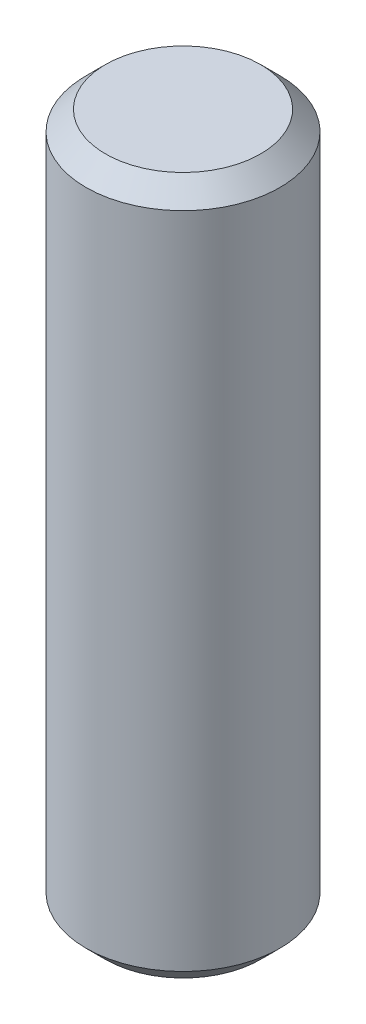
SolidWorks part; units mm, degrees
ref_plane "前视基准面" through (0, 0, 0) normal (0, 0, 1) x (1, 0, 0)
ref_plane "上视基准面" through (0, 0, 0) normal (0, 1, 0) x (1, 0, 0)
ref_plane "右视基准面" through (0, 0, 0) normal (1, 0, 0) x (0, 0, -1)
other "Configuration Table"
sketch "草图1" plane through (0, 0, 0) normal (0, 0, 1) x (1, 0, 0)
  line L0 (0, 23.0737) -> (0, -19.8109) construction
  line L1 (0, 23) -> (5, 23)
  line L2 (5, 23) -> (5, 5)
  line L4 (5, 5) -> (5, 0)
  line L6 (5, 0) -> (5, -13)
  line L7 (5, -13) -> (0, -13)
  line L8 (0, 23) -> (0, -13)
  point P5 (5, -4.7271)
  point P7 (5, 0)
  dimension "D1" = 5
  dimension "D2" = 36
  dimension "D3" = 5
  dimension "D4" = 13
revolve "旋转1" add sketch "草图1" angle 360 about L0
chamfer "倒角1" distance 1 angle 45 2 edges at (0, -13, 5) (0, 23, 5)
